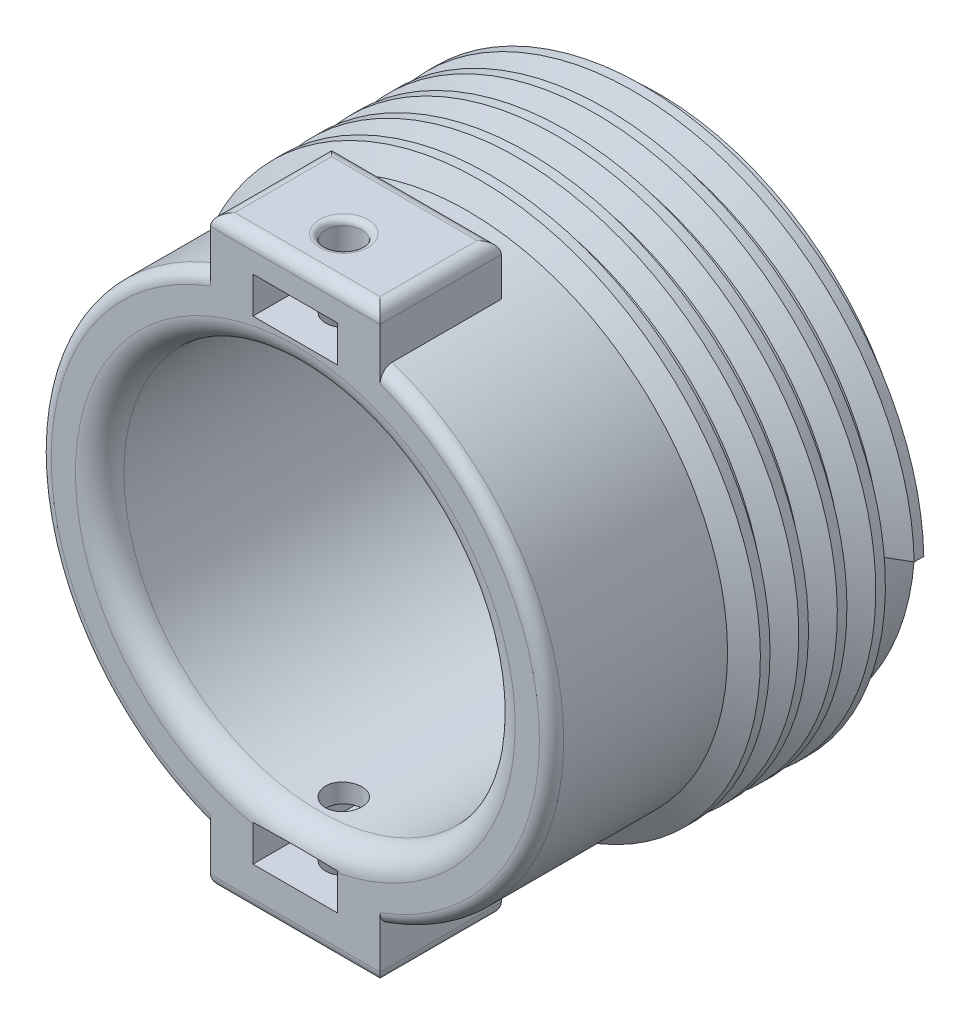
SolidWorks part; units mm, degrees
ref_plane "Plano frontal" through (0, 0, 0) normal (0, 0, 1) x (1, 0, 0)
ref_plane "Plano superior" through (0, 0, 0) normal (0, 1, 0) x (1, 0, 0)
ref_plane "Plano direito" through (0, 0, 0) normal (1, 0, 0) x (0, 0, -1)
sketch "Esboço1" plane through (0, 0, 0) normal (0, 0, 1) x (1, 0, 0)
  circle A0 centre (0, 0) radius 16.15
  circle A1 centre (0, 0) radius 21.15
  dimension "D1" = 32.3
  dimension "D2" = 42.3
extrude "Ressalto-extrusão1" add sketch "Esboço1" along normal blind 30
fillet "Filete1" radius 2 1 edges at (16.15, 0, 30)
fillet "Filete2" radius 1 1 edges at (21.15, 0, 30)
thread "Rosca1" pitch 3.175 method extrude profile "Perfil da rosca1" start angle 0, offset 0.0001, length 15, pitch 3.175, diameter 42.3
ref_plane "Plano1" through (21.15, 0, -0.0001) normal (0, 1, 0) x (-1, 0, 0)
sketch "Perfil da rosca1" plane through (21.15, 0, -0.0001) normal (0, 1, 0) x (-1, 0, 0)
  line L0 (0, 0) -> (0, 3.175) construction
  line L11 (0, 0) -> (0, 2.7781)
  line L12 (0, 2.7781) -> (-1.7185, 1.7859)
  line L13 (-1.7185, 1.7859) -> (-1.7185, 0.9922)
  line L15 (-1.7185, 0.9922) -> (0, 0)
  line L17 (-1.7185, 1.3891) -> (0, 1.3891) construction
  point P2 (0, 0)
  dimension "Pitch" = 3.175
  dimension "Profile_Angle" = 60
  dimension "Profile_Land" = 0.7937
  dimension "Profile_Height" = 1.7185
ref_plane "Plano2" through (0, 0, 25) normal (0, 0, 1) x (1, 0, 0)
sketch "Esboço4" plane through (0, 0, 25) normal (0, 0, 1) x (1, 0, 0)
  line L0 (0, 0) -> (22.8685, 0) construction
  line L1 (-7, -24.15) -> (7, -24.15)
  line L2 (-7, -24.15) -> (-7, -18.15)
  line L4 (7, -24.15) -> (7, -18.15)
  line L5 (-7, -24.15) -> (1.6667, -18.15) construction
  line L6 (-1.6667, -18.15) -> (7, -24.15) construction
  line L7 (-1.6667, 18.15) -> (7, 24.15) construction
  line L8 (-7, 24.15) -> (1.6667, 18.15) construction
  line L9 (7, 24.15) -> (7, 18.15)
  line L11 (-7, 24.15) -> (-7, 18.15)
  line L12 (-7, 24.15) -> (7, 24.15)
  line L13 (-7, 18.15) -> (7, 18.15)
  line L14 (-7, -18.15) -> (7, -18.15)
  point P0 (0, -19.3038)
  point P1 (0, 24.15)
  point P15 (0, 19.3038)
  point P19 (0, 18.15)
  point P22 (0, -18.15)
  dimension "D1" = 6
  dimension "D2" = 14
extrude "Ressalto-extrusão2" add sketch "Esboço4" along normal blind 5 and the other way blind 5
sketch "Esboço5" plane through (0, 24.15, 0) normal (0, 1, 0) x (1, 0, 0)
  line L0 (7, -30) -> (-7, -30) construction
  line L1 (0, -20) -> (0, -30) construction
  line L2 (7, -20) -> (-7, -20) construction
  circle A0 centre (0, -26) radius 1.5
  point P5 (0, -30)
  dimension "D1" = 3
  dimension "D2" = 4
extrude "Corte-extrusão1" cut sketch "Esboço5" against normal through all
sketch "Esboço6" plane through (0, 0, 30) normal (0, 0, 1) x (1, 0, 0)
  line L1 (-3.5, 21.5) -> (3.5, 21.5)
  line L2 (-3.5, 21.5) -> (-3.5, 18.5)
  line L3 (-3.5, 18.5) -> (3.5, 18.5)
  line L4 (3.5, 21.5) -> (3.5, 18.5)
  line L5 (-3.5, 21.5) -> (3.5, 18.5) construction
  line L6 (-3.5, 18.5) -> (3.5, 21.5) construction
  line L7 (-3.5, -17.6769) -> (3.5, -17.6769)
  line L8 (-3.5, -17.6769) -> (-3.5, -20.6769)
  line L9 (-3.5, -20.6769) -> (3.5, -20.6769)
  line L10 (3.5, -17.6769) -> (3.5, -20.6769)
  line L11 (-3.5, -17.6769) -> (3.5, -20.6769) construction
  line L12 (-3.5, -20.6769) -> (3.5, -17.6769) construction
  point P0 (0, 20)
  point P5 (0, -19.1769)
  dimension "D1" = 3
  dimension "D2" = 7
  dimension "D3" = 20
extrude "Corte-extrusão2" cut sketch "Esboço6" against normal blind 8.5
fillet "Filete3" radius 1 8 edges at (0, 24.15, 20) (7, 24.15, 25) (0, 24.15, 30) (-7, 24.15, 25) (0, -24.15, 20) (-7, -24.15, 25) (0, -24.15, 30) (7, -24.15, 25)
fillet "Filete4" radius 0.5 2 edges at (-1.5, 24.15, 26) (-1.5, -24.15, 26)
chamfer "Chanfro1" distance 3 angle 45 rebuild error yes
